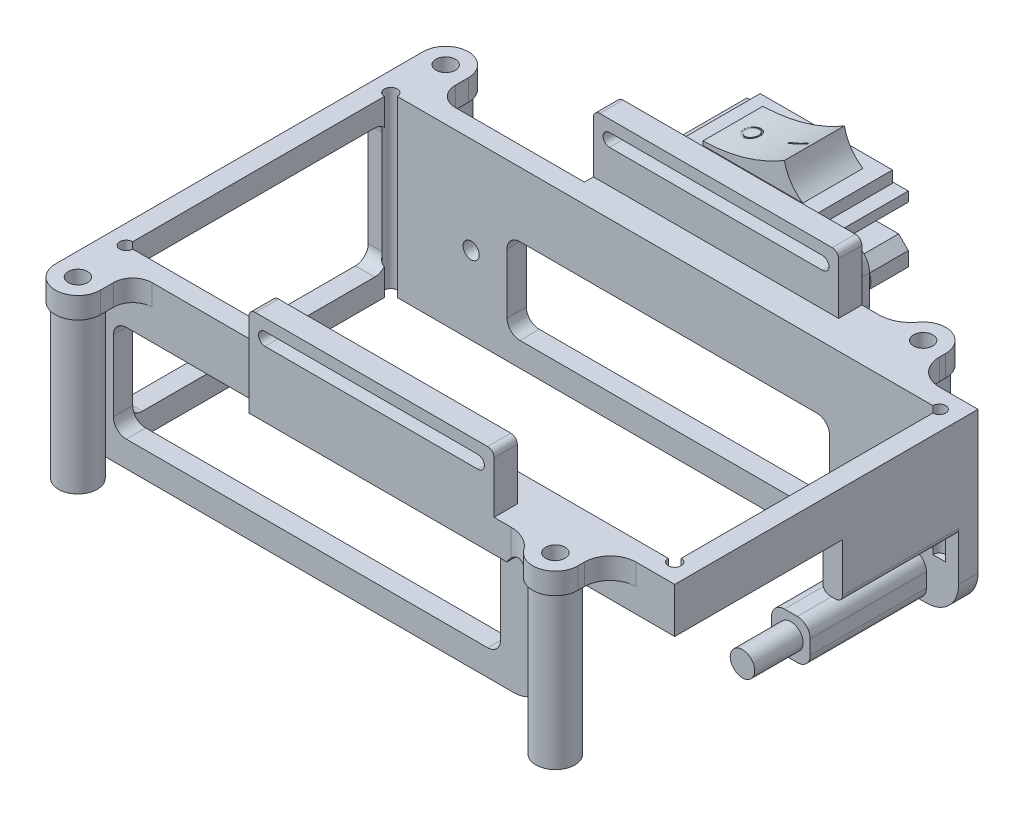
SolidWorks part; units mm, degrees
ref_plane "前视基准面" through (0, 0, 0) normal (0, 0, 1) x (1, 0, 0)
ref_plane "上视基准面" through (0, 0, 0) normal (0, 1, 0) x (1, 0, 0)
ref_plane "右视基准面" through (0, 0, 0) normal (1, 0, 0) x (0, 0, -1)
sketch "草图1" plane through (0, 0, 0) normal (0, 1, 0) x (1, 0, 0)
  line L0 (-106.1667, 0) -> (179.4722, 0) construction
  line L1 (0, 90.2417) -> (0, -97.825) construction
  line L2 (-41.5, 20.5) -> (41.5, 20.5)
  line L3 (-45.5, 23.5) -> (45.5, 23.5)
  line L4 (-45.5, 23.5) -> (-45.5, -23.5)
  line L5 (-45.5, -23.5) -> (45.5, -23.5)
  line L6 (45.5, 23.5) -> (45.5, -23.5)
  line L7 (-45.5, 23.5) -> (45.5, -23.5) construction
  line L8 (-45.5, -23.5) -> (45.5, 23.5) construction
  line L9 (42.5, 19.5) -> (42.5, -19.5)
  line L10 (-41.5, -20.5) -> (41.5, -20.5)
  line L11 (-42.5, 19.5) -> (-42.5, -19.5)
  line L13 (-42.5, 20.5) -> (42.5, 20.5) construction
  line L14 (-42.5, 20.5) -> (-42.5, -20.5) construction
  line L15 (-42.5, -20.5) -> (42.5, -20.5) construction
  line L16 (42.5, 20.5) -> (42.5, -20.5) construction
  arc A0 (-41.5, 20.5) -> (-42.5, 19.5) centre (-42.5, 20.5) ccw
  arc A1 (41.5, 20.5) -> (42.5, 19.5) centre (42.5, 20.5) cw
  arc A2 (41.5, -20.5) -> (42.5, -19.5) centre (42.5, -20.5) ccw
  arc A3 (-41.5, -20.5) -> (-42.5, -19.5) centre (-42.5, -20.5) cw
  point P5 (0, 0)
  point P18 (-42.5, 21.5)
  dimension "D4" = 2
  dimension "D1" = 91
  dimension "D2" = 47
  dimension "D3" = 3
extrude "凸台-拉伸1" add sketch "草图1" along normal blind 27
sketch "草图2" plane through (0, 27, 0) normal (0, 1, 0) x (1, 0, 0)
  line L0 (-64.1673, 0) -> (79.9623, 0) construction
  line L1 (-45.5, -28.5) -> (-45.5, -23.5)
  line L2 (-45.5, 23.5) -> (-45.5, -23.5) construction
  line L3 (-38.5, 28.5) -> (-38.5, 26.5)
  line L5 (-45.5, -23.5) -> (-35.5, -23.5)
  line L6 (-45.5, 23.5) -> (-35.5, 23.5)
  line L7 (-38.5, -28.5) -> (-38.5, -26.5)
  line L8 (-5, 39.0531) -> (-5, -39.5724) construction
  line L9 (28.5, -28.5) -> (28.5, -23.5)
  line L10 (35.5, 23.5) -> (28.5, 23.5)
  line L11 (35.5, -23.5) -> (28.5, -23.5)
  line L12 (28.5, 28.5) -> (28.5, 23.5)
  line L13 (35.5, -28.5) -> (35.5, -23.5)
  line L14 (35.5, 23.5) -> (35.5, 28.5)
  line L15 (-45.5, 23.5) -> (-45.5, 28.5)
  line L16 (-45.5, -23.5) -> (45.5, -23.5) construction
  line L17 (45.5, 23.5) -> (-45.5, 23.5) construction
  circle A0 centre (-42, 28.5) radius 3.5
  arc A1 (-35.5, 23.5) -> (-38.5, 26.5) centre (-35.5, 26.5) cw
  circle A2 centre (-42, 28.5) radius 1.5
  circle A3 centre (-42, -28.5) radius 1.5
  arc A4 (-35.5, -23.5) -> (-38.5, -26.5) centre (-35.5, -26.5) ccw
  circle A5 centre (-42, -28.5) radius 3.5
  circle A6 centre (32, -28.5) radius 3.5
  circle A8 centre (32, -28.5) radius 1.5
  circle A9 centre (32, 28.5) radius 1.5
  circle A11 centre (32, 28.5) radius 3.5
  point P12 (-45.5, 0)
  point P28 (-42, 32)
  point P29 (-42, -32)
  point P47 (32, -32)
  point P48 (32, 32)
  point P49 (35.5, 0)
  line M2 (45.5, 23.5) -> (-45.5, 23.5)
  line M4 (-45.5, -23.5) -> (45.5, -23.5)
  dimension "D1" = 7
  dimension "D2" = 3
  dimension "D4" = 3
  dimension "D3" = 64
  dimension "D5" = 81
extrude "凸台-拉伸2" add sketch "草图2" against normal blind 3.3 contours A1 L3 A0 L15 M2 | A0 A2 | L14 A11 L12 M2 | A11 A9 | A5 A3 | L1 A5 L7 A4 M4 | A6 A8 | L9 A6 L13 M4 region at (32, 27, 24.7611) region at (-41.5447, 27, 24.6966) region at (-42, 27, 25.099) region at (32, 27, 25.099) region at (32, 27, -24.7611) region at (-42, 27, -25.099) region at (-41.5447, 27, -24.6966) region at (32, 27, -31.901)
sketch "草图3" plane through (0, 0, 23.5) normal (0, 0, 1) x (1, 0, 0)
  line L0 (-51.5907, 19) -> (64.9706, 19) construction
  line L1 (-14.5, 36) -> (21.5, 36)
  line L2 (-15.5, 35) -> (-15.5, 22)
  line L3 (-15.5, 22) -> (22.5, 22)
  line L4 (22.5, 35) -> (22.5, 22)
  line L5 (-35.5, 27) -> (28.5, 27) construction
  line L6 (35.5, 23.7) -> (35.5, 27) construction
  line L7 (-13, 33.2) -> (20, 33.2) construction
  line L8 (22.5, 22) -> (24.5, 22)
  line L9 (22.5, 22) -> (22.5, 27)
  line L10 (22.5, 27) -> (24.5, 27)
  line L11 (24.5, 22) -> (24.5, 27)
  line L12 (24.5, 27) -> (28.5, 27)
  line L13 (24.5, 27) -> (24.5, 23.7)
  line L14 (24.5, 23.7) -> (28.5, 23.7)
  line L15 (28.5, 27) -> (28.5, 23.7)
  line L16 (-13, 34.2) -> (20, 34.2)
  line L17 (-13, 32.2) -> (20, 32.2)
  arc A0 (-13, 34.2) -> (-13, 32.2) centre (-13, 33.2) ccw
  arc A1 (20, 32.2) -> (20, 34.2) centre (20, 33.2) ccw
  arc A2 (22.5, 35) -> (21.5, 36) centre (21.5, 35) ccw
  arc A3 (-15.5, 35) -> (-14.5, 36) centre (-14.5, 35) cw
  point P19 (3.5, 33.2)
  point P24 (-14, 33.2)
  point P25 (21, 33.2)
  line M1 (28.5, 23.7) -> (28.5, 27)
  line M2 (28.5, 27) -> (-35.5, 27)
  dimension "D11" = 1
  dimension "D1" = 14
  dimension "D2" = 8
  dimension "D3" = 3
  dimension "D4" = 51
  dimension "D5" = 38
  dimension "D6" = 40
  dimension "D7" = 2
  dimension "D8" = 35
  dimension "D9" = 1.5
  dimension "D10" = 1.8
extrude "凸台-拉伸3" add sketch "草图3" along normal blind 5 contours A3 L2 L4 A2 L1 A1 L17 A0 L16 M2 | L4 L2 L3 M2 | L8 L11 L4 M2 | L11 L14 M1 M2 region at (3.5, 31.0618, 23.5) region at (3.5, 24.5, 23.5) region at (23.5, 24.5, 23.5) region at (26.5, 25.35, 23.5)
sketch "草图4" plane through (0, 0, 23.5) normal (0, 0, -1) x (-1, 0, 0)
  line L4 (-22.5, 27) -> (15.5, 27)
  line L5 (15.5, 27) -> (15.5, 35)
  line L6 (14.5, 36) -> (-21.5, 36)
  line L7 (-22.5, 35) -> (-22.5, 27)
  line L8 (-22.5, 27) -> (15.5, 27)
  line L9 (15.5, 27) -> (15.5, 35)
  line L10 (14.5, 36) -> (-21.5, 36)
  line L11 (-22.5, 35) -> (-22.5, 27)
  arc A2 (15.5, 35) -> (14.5, 36) centre (14.5, 35) ccw
  arc A3 (-21.5, 36) -> (-22.5, 35) centre (-21.5, 35) ccw
  arc A4 (15.5, 35) -> (14.5, 36) centre (14.5, 35) ccw
  arc A5 (-21.5, 36) -> (-22.5, 35) centre (-21.5, 35) ccw
  dimension "D1" = 0
extrude "切除-拉伸1" cut sketch "草图4" against normal blind 1.4
fillet "圆角1" radius 3 1 edges at (24.5, 23.7, 26)
fillet "圆角2" radius 5 1 edges at (28.5, 25.35, 28.5)
fillet "圆角3" radius 4 1 edges at (35.5, 25.35, 23.5)
mirror "镜向3" about plane through (0, 0, 0) normal (0, 0, 1) of "切除-拉伸1", "凸台-拉伸3"
fillet "圆角4" radius 5 1 edges at (28.5, 25.35, -28.5)
fillet "圆角5" radius 4 1 edges at (35.5, 25.35, -23.5)
fillet "圆角6" radius 3 1 edges at (24.5, 23.7, -26)
sketch "草图5" plane through (-45.5, 0, 0) normal (-1, 0, 0) x (0, 0, 1)
  line L0 (0, 27) -> (0, -23.0063) construction
  line L1 (-28.5, 27) -> (28.5, 27) construction
  line L2 (23.5, 23.7) -> (23.5, 0) construction
  line L3 (-18, 23.5) -> (18, 23.5)
  line L4 (-20, 21.5) -> (-20, 5.5)
  line L5 (-18, 3.5) -> (18, 3.5)
  line L6 (20, 21.5) -> (20, 5.5)
  line L7 (-20, 23.5) -> (20, 3.5) construction
  line L8 (-20, 3.5) -> (20, 23.5) construction
  line L9 (-23.5, 0) -> (23.5, 0) construction
  arc A0 (18, 23.5) -> (20, 21.5) centre (18, 21.5) cw
  arc A1 (20, 5.5) -> (18, 3.5) centre (18, 5.5) cw
  arc A2 (-18, 3.5) -> (-20, 5.5) centre (-18, 5.5) cw
  arc A3 (-20, 21.5) -> (-18, 23.5) centre (-18, 21.5) cw
  point P5 (0, 13.5)
  dimension "D4" = 2
  dimension "D1" = 3.5
  dimension "D2" = 3.5
  dimension "D3" = 3.5
extrude "切除-拉伸2" cut sketch "草图5" against normal blind 18.4
sketch "草图6" plane through (0, 0, -23.5) normal (0, 0, -1) x (-1, 0, 0)
  line L0 (-45.5, 27) -> (-45.5, 0) construction
  line L1 (-23.5, 17) -> (22.5, 17)
  line L2 (-25.5, 15) -> (-25.5, 5.75)
  line L3 (-23.5, 3.75) -> (22.5, 3.75)
  line L4 (24.5, 15) -> (24.5, 5.75)
  line L5 (-25.5, 17) -> (24.5, 3.75) construction
  line L6 (-25.5, 3.75) -> (24.5, 17) construction
  line L7 (45.5, 23.7) -> (45.5, 0) construction
  line L8 (-45.5, 0) -> (45.5, 0) construction
  line L9 (15.5, 27) -> (35.5, 27) construction
  line L10 (-0.5, 17) -> (-0.5, 3.75) construction
  arc A0 (22.5, 17) -> (24.5, 15) centre (22.5, 15) cw
  arc A1 (24.5, 5.75) -> (22.5, 3.75) centre (22.5, 5.75) cw
  arc A2 (-23.5, 3.75) -> (-25.5, 5.75) centre (-23.5, 5.75) cw
  arc A3 (-25.5, 15) -> (-23.5, 17) centre (-23.5, 15) cw
  circle A4 centre (-31.05, 12.05) radius 1.25
  circle A5 centre (30.05, 12.05) radius 1.25
  point P0 (-0.5, 10.375)
  point P31 (30.05, 13.3)
  point P32 (28.8, 12.05)
  dimension "D5" = 2
  dimension "D6" = 2.5
  dimension "D1" = 20
  dimension "D2" = 21
  dimension "D3" = 3.75
  dimension "D4" = 10
  dimension "D7" = 13.7
  dimension "D8" = 4.3
extrude "切除-拉伸3" cut sketch "草图6" against normal blind 18.4
sketch "草图7" plane through (0, 0, 23.5) normal (0, 0, 1) x (1, 0, 0)
  line L0 (-45.5, 23.7) -> (-45.5, 0) construction
  line L1 (-39.5, 19) -> (16.5, 19)
  line L2 (-41.5, 17) -> (-41.5, 6)
  line L3 (-39.5, 4) -> (16.5, 4)
  line L4 (18.5, 17) -> (18.5, 6)
  line L5 (-41.5, 19) -> (18.5, 4) construction
  line L6 (-41.5, 4) -> (18.5, 19) construction
  line L7 (-45.5, 0) -> (45.5, 0) construction
  line L8 (-35.5, 27) -> (-15.5, 27) construction
  line L9 (45.5, 27) -> (45.5, 0) construction
  arc A0 (16.5, 19) -> (18.5, 17) centre (16.5, 17) cw
  arc A1 (16.5, 4) -> (18.5, 6) centre (16.5, 6) ccw
  arc A2 (-39.5, 4) -> (-41.5, 6) centre (-39.5, 6) cw
  arc A3 (-41.5, 17) -> (-39.5, 19) centre (-39.5, 17) cw
  point P0 (-11.5, 11.5)
  dimension "D5" = 2
  dimension "D1" = 4
  dimension "D2" = 4
  dimension "D3" = 8
  dimension "D4" = 27
extrude "切除-拉伸4" cut sketch "草图7" against normal blind 18.4
sketch "草图8" plane through (0, 0, 23.5) normal (0, 0, 1) x (1, 0, 0)
  line L0 (39.5, 27) -> (45.5, 27) construction
  line L1 (45.5, 0) -> (25.5, 0)
  line L2 (45.5, 0) -> (45.5, 20)
  line L3 (45.5, 20) -> (30.5, 20)
  line L4 (25.5, 0) -> (25.5, 15)
  line L5 (18.5, 6) -> (18.5, 17) construction
  arc A0 (25.5, 15) -> (30.5, 20) centre (30.5, 15) cw
  dimension "D3" = 5
  dimension "D1" = 7
  dimension "D2" = 7
extrude "切除-拉伸5" cut sketch "草图8" against normal blind 26
fillet "圆角7" radius 5 1 edges at (25.5, 0, 22)
sketch "草图9" plane through (0, 0, -2.5) normal (0, 0, 1) x (1, 0, 0)
  line L0 (42.5, 20) -> (42.5, 0) construction
  line L1 (45.5, 0) -> (42.5, 0)
  line L2 (45.5, 0) -> (45.5, 11.5)
  line L3 (45.5, 11.5) -> (42.5, 11.5)
  line L4 (42.5, 0) -> (42.5, 11.5)
  line L5 (39.5, 27) -> (45.5, 27) construction
  dimension "D1" = 15.5
extrude "切除-拉伸6" cut sketch "草图9" against normal blind 18
fillet "圆角8" radius 1 2 edges at (42.5, 11.5, -11) (45.5, 11.5, -11.5)
sketch "草图10" plane through (0, 0, 0) normal (0, -1, 0) x (1, 0, 0)
  line L0 (41.5, -20.5) -> (-41.5, -20.5) construction
  line L1 (45.5, -23.5) -> (35.5, -23.5)
  line L2 (45.5, -23.5) -> (45.5, -20.5)
  line L3 (45.5, -20.5) -> (35.5, -20.5)
  line L4 (35.5, -23.5) -> (35.5, -20.5)
  dimension "D1" = 10
extrude "凸台-拉伸4" add sketch "草图10" against normal blind 7
fillet "圆角9" radius 5 1 edges at (45.5, 0, -22)
sketch "草图11" plane through (0, 0, -20.5) normal (0, 0, 1) x (1, 0, 0)
  line L0 (40.5, 0) -> (-41.5, 0) construction
  line L1 (38.5, 0) -> (36.5, 0)
  line L2 (40.5, 2) -> (40.5, 4.2)
  line L3 (38.5, 6.2) -> (36.5, 6.2)
  line L4 (34.5, 2) -> (34.5, 4.2)
  line L5 (45.5, 5) -> (45.5, 12.5) construction
  arc A0 (40.5, 4.2) -> (38.5, 6.2) centre (38.5, 4.2) ccw
  arc A1 (36.5, 6.2) -> (34.5, 4.2) centre (36.5, 4.2) ccw
  arc A2 (34.5, 2) -> (36.5, 0) centre (36.5, 2) ccw
  arc A3 (38.5, 0) -> (40.5, 2) centre (38.5, 2) ccw
  point P10 (40.5, 6.2)
  point P13 (34.5, 6.2)
  point P18 (40.5, 0)
  dimension "D4" = 2
  dimension "D1" = 6
  dimension "D2" = 6.2
  dimension "D3" = 11
extrude "凸台-拉伸5" add sketch "草图11" along normal blind 18
sketch "草图12" plane through (0, 0, -2.5) normal (0, 0, 1) x (1, 0, 0)
  line L0 (34.5, 3.1) -> (40.5, 3.1) construction
  line L1 (34.5, 4.2) -> (34.5, 2) construction
  line L2 (40.5, 2) -> (40.5, 4.2) construction
  line L3 (37.5, 6.2) -> (37.5, 0) construction
  line L4 (38.5, 6.2) -> (36.5, 6.2) construction
  line L5 (36.5, 0) -> (38.5, 0) construction
  circle A0 centre (37.5, 3.1) radius 1.9
  dimension "D1" = 3.8
extrude "凸台-拉伸6" add sketch "草图12" along normal blind 7.5
sketch "草图13" plane through (0, 23.7, 0) normal (0, -1, 0) x (1, 0, 0)
  circle A0 centre (-42, 28.5) radius 3
  circle A1 centre (32, 28.5) radius 3
  circle A2 centre (32, -28.5) radius 3
  circle A3 centre (-42, -28.5) radius 3
  circle A4 centre (-42, 28.5) radius 1.5 construction
  circle A5 centre (-42, -28.5) radius 1.5 construction
  circle A6 centre (32, -28.5) radius 1.5 construction
  circle A7 centre (32, 28.5) radius 1.5 construction
  circle A8 centre (-42, 28.5) radius 1.5
  circle A9 centre (-42, -28.5) radius 1.5
  circle A10 centre (32, -28.5) radius 1.5
  circle A11 centre (32, 28.5) radius 1.5
  dimension "D1" = 6
extrude "凸台-拉伸7" add sketch "草图13" along normal up to surface (23.7 mm away) up to face at (0.7561, 0, -3.2857)
sketch "草图14" plane through (0, 0, -28.5) normal (0, 0, -1) x (-1, 0, 0)
  line L0 (15.5, 22) -> (-24.5, 22) construction
  line L1 (-18, 32.2) -> (11, 32.2)
  line L2 (-21, 29.2) -> (-21, 25)
  line L3 (-18, 22) -> (11, 22)
  line L4 (14, 29.2) -> (14, 25)
  line L5 (-21, 32.2) -> (14, 22) construction
  line L6 (-21, 22) -> (14, 32.2) construction
  line L7 (13, 32.2) -> (-20, 32.2) construction
  line L8 (-3.5, 36) -> (-3.5, 9.834) construction
  line L9 (14.5, 36) -> (-21.5, 36) construction
  arc A0 (11, 22) -> (14, 25) centre (11, 25) ccw
  arc A1 (11, 32.2) -> (14, 29.2) centre (11, 29.2) cw
  arc A2 (-18, 22) -> (-21, 25) centre (-18, 25) cw
  arc A3 (-21, 29.2) -> (-18, 32.2) centre (-18, 29.2) cw
  point P0 (-3.5, 27.1)
  dimension "D2" = 3
  dimension "D1" = 35
extrude "凸台-拉伸8" add sketch "草图14" along normal blind 2.7
sketch "草图15" plane through (0, 0, -31.2) normal (0, 0, -1) x (-1, 0, 0)
  line L0 (-21, 27.1) -> (14, 27.1) construction
  line L1 (-21, 29.2) -> (-21, 25) construction
  line L2 (14, 25) -> (14, 29.2) construction
  line L3 (-3.5, 32.2) -> (-3.5, 22) construction
  line L4 (11, 32.2) -> (-18, 32.2) construction
  line L5 (-18, 22) -> (11, 22) construction
  line L6 (-21, 29.2) -> (-21, 25) construction
  line L7 (11.8547, 27.1) -> (11.2774, 26.1)
  line L8 (-16.5453, 27.1) -> (-17.1226, 28.1)
  line L9 (-17.1226, 28.1) -> (-18.2774, 28.1)
  line L10 (-18.2774, 28.1) -> (-18.8547, 27.1)
  line L11 (-18.8547, 27.1) -> (-18.2774, 26.1)
  line L12 (-18.2774, 26.1) -> (-17.1226, 26.1)
  line L13 (-17.1226, 26.1) -> (-16.5453, 27.1)
  line L14 (11.2774, 28.1) -> (11.8547, 27.1)
  line L15 (10.1226, 26.1) -> (9.5453, 27.1)
  line L16 (11.2774, 26.1) -> (10.1226, 26.1)
  line L17 (10.1226, 28.1) -> (11.2774, 28.1)
  line L18 (9.5453, 27.1) -> (10.1226, 28.1)
  circle A0 centre (-17.7, 27.1) radius 2.5
  circle A1 centre (10.7, 27.1) radius 2.5
  circle A2 centre (-17.7, 27.1) radius 1 construction
  circle A3 centre (10.7, 27.1) radius 1 construction
  dimension "D2" = 5
  dimension "D1" = 3.3
  dimension "D3" = 2
extrude "凸台-拉伸9" add sketch "草图15" along normal blind 1
sketch "草图17" plane through (0, 0, -31.2) normal (0, 0, -1) x (-1, 0, 0)
  line L0 (-21, 27.1) -> (14, 27.1) construction
  line L1 (-21, 29.2) -> (-21, 25) construction
  line L2 (14, 25) -> (14, 29.2) construction
  line L3 (-3.5, 32.2) -> (-3.5, 22) construction
  line L4 (11, 32.2) -> (-18, 32.2) construction
  line L5 (-18, 22) -> (11, 22) construction
  line L6 (15.5, 22) -> (-24.5, 22) construction
  line L7 (-16, 32.2) -> (9, 32.2) construction
  line L8 (-16, 32.2) -> (-16, 22) construction
  line L9 (-16, 22) -> (9, 22) construction
  line L10 (9, 32.2) -> (9, 22) construction
  line L11 (-16, 32.2) -> (9, 22) construction
  line L12 (-16, 22) -> (9, 32.2) construction
  line L13 (-16, 24.2) -> (-16, 22)
  line L14 (-16, 30.7) -> (-10.5, 30.7)
  line L15 (-16, 24.2) -> (-14.5, 25.7)
  line L16 (-14.5, 25.7) -> (-10.5, 25.7)
  line L17 (-9.5, 29.7) -> (-9.5, 26.7)
  line L18 (-16, 22) -> (9, 22)
  line L19 (-16, 30.7) -> (-16, 32.2)
  line L20 (-16, 32.2) -> (9, 32.2)
  line L21 (9, 30.7) -> (9, 32.2)
  line L22 (9, 24.2) -> (9, 22)
  line L23 (9, 24.2) -> (7.5, 25.7)
  line L24 (7.5, 25.7) -> (3.5, 25.7)
  line L25 (2.5, 29.7) -> (2.5, 26.7)
  line L26 (9, 30.7) -> (3.5, 30.7)
  circle A0 centre (-3.5, 27.1) radius 1.25
  arc A1 (-10.5, 25.7) -> (-9.5, 26.7) centre (-10.5, 26.7) ccw
  arc A2 (-9.5, 29.7) -> (-10.5, 30.7) centre (-10.5, 29.7) ccw
  arc A3 (3.5, 25.7) -> (2.5, 26.7) centre (3.5, 26.7) cw
  arc A4 (2.5, 29.7) -> (3.5, 30.7) centre (3.5, 29.7) cw
  point P12 (-3.5, 27.1)
  point P23 (-16, 25.7)
  dimension "D2" = 2.5
  dimension "D6" = 1
  dimension "D1" = 25
  dimension "D3" = 6
  dimension "D4" = 1.5
  dimension "D5" = 5
extrude "凸台-拉伸10" add sketch "草图17" along normal blind 11
sketch "草图18" plane through (0, 32.2, 0) normal (0, 1, 0) x (1, 0, 0)
  line L0 (3.5, 42.2) -> (3.5, 28.526) construction
  line L1 (-9, 42.2) -> (16, 42.2) construction
  line L2 (-14.5, 28.5) -> (21.5, 28.5) construction
  line L3 (-6.75, 42) -> (13.75, 42)
  line L4 (-6.75, 42) -> (-6.75, 28.5)
  line L5 (-6.75, 28.5) -> (13.75, 28.5)
  line L6 (13.75, 42) -> (13.75, 28.5)
  line L7 (-6.75, 42) -> (13.75, 28.5) construction
  line L8 (-6.75, 28.5) -> (13.75, 42) construction
  point P4 (3.5, 35.25)
  dimension "D1" = 13.5
  dimension "D2" = 20.5
extrude "凸台-拉伸12" add sketch "草图18" along normal blind 1.8
ref_plane "基准面1" through (0, 0, -35.25) normal (0, 0, -1) x (-1, 0, 0)
sketch "草图19" plane through (0, 0, -35.25) normal (0, 0, -1) x (-1, 0, 0)
  line L0 (-3.5, 34) -> (-3.5, 29.3251) construction
  line L1 (-13.75, 34) -> (6.75, 34) construction
  line L2 (4.25, 34) -> (-11.25, 34)
  line L3 (-16, 22) -> (9, 22) construction
  line L4 (4.25, 34) -> (4.25, 34.5923)
  line L5 (14.5, 36) -> (-21.5, 36) construction
  spline S0 degree 2 poles (-11.25, 34) (-8.9724, 35.5986) (-8.4021, 38.3) knots 0 0 0 1 1 1
  spline S1 degree 2 poles (-8.4021, 38.3) (-2.5984, 34.811) (4.25, 34.5923) knots 0 0 0 1 1 1
  dimension "D1" = 16.3
  dimension "D2" = 15.5
extrude "凸台-拉伸13" add sketch "草图19" along normal mid plane 9.3
ref_plane "基准面2" through (0, 44, 0) normal (0, 1, 0) x (1, 0, 0)
sketch "草图20" plane through (0, 44, 0) normal (0, 1, 0) x (1, 0, 0)
  line L0 (-4.25, 35.25) -> (11.25, 35.25) construction
  line L1 (-4.25, 39.9) -> (-4.25, 30.6) construction
  line L2 (11.25, 39.9) -> (11.25, 30.6) construction
  line L3 (-4.25, 39.9) -> (-4.25, 30.6) construction
  line L4 (8.4021, 39.9) -> (8.4021, 30.6) construction
  line L5 (4.4021, 35.375) -> (7.4021, 35.375)
  line L6 (4.4021, 35.375) -> (4.4021, 35.125)
  line L7 (4.4021, 35.125) -> (7.4021, 35.125)
  line L8 (7.4021, 35.375) -> (7.4021, 35.125)
  line L9 (4.4021, 35.375) -> (7.4021, 35.125) construction
  line L10 (4.4021, 35.125) -> (7.4021, 35.375) construction
  circle A0 centre (-1.25, 35.25) radius 1.25
  circle A1 centre (-1.25, 35.25) radius 1
  point P11 (5.9021, 35.25)
  dimension "D1" = 2
  dimension "D2" = 2.5
  dimension "D3" = 3
  dimension "D4" = 0.25
  dimension "D5" = 3
  dimension "D6" = 2.5
extrude "切除-拉伸7" cut sketch "草图20" against normal blind 9.3
